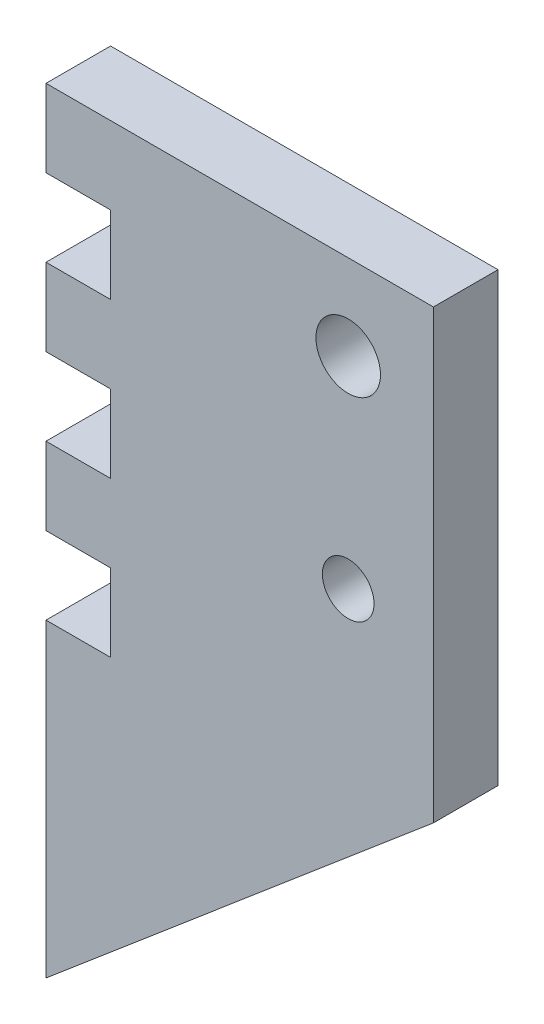
SolidWorks part; units mm, degrees
ref_plane "Front Plane" through (0, 0, 0) normal (0, 0, 1) x (1, 0, 0)
ref_plane "Top Plane" through (0, 0, 0) normal (0, 1, 0) x (1, 0, 0)
ref_plane "Right Plane" through (0, 0, 0) normal (1, 0, 0) x (0, 0, -1)
sketch "Sketch1" plane through (0, 0, 0) normal (0, 0, 1) x (1, 0, 0)
  line L0 (0, 0) -> (-38.1, 0)
  line L1 (0, 0) -> (0, -43.942)
  line L2 (-38.1, 0) -> (-38.1, -7.62)
  line L3 (-38.1, -7.62) -> (-31.75, -7.62)
  line L4 (-31.75, -7.62) -> (-31.75, -15.24)
  line L5 (-31.75, -15.24) -> (-38.1, -15.24)
  line L6 (-38.1, -45.72) -> (-38.1, -76.2)
  line L7 (-38.1, -15.24) -> (-38.1, -22.86)
  line L8 (-38.1, -22.86) -> (-31.75, -22.86)
  line L9 (-31.75, -22.86) -> (-31.75, -30.48)
  line L10 (-31.75, -30.48) -> (-38.1, -30.48)
  line L11 (-38.1, -30.48) -> (-38.1, -38.1)
  line L12 (-38.1, -38.1) -> (-31.75, -38.1)
  line L13 (-31.75, -38.1) -> (-31.75, -45.72)
  line L14 (-31.75, -45.72) -> (-38.1, -45.72)
  line L15 (-38.1, -76.2) -> (0, -43.942)
  circle A0 centre (-8.382, -8.382) radius 3.175
  circle A1 centre (-8.382, -28.194) radius 2.54
  point P23 (0, 0)
  point P24 (0, 0)
  dimension "D9" = 6.35
  dimension "D10" = 5.08
  dimension "D1" = 38.1
  dimension "D2" = 43.942
  dimension "D3" = 7.62
  dimension "D4" = 7.62
  dimension "D5" = 6.35
  dimension "D6" = 6.35
  dimension "D8" = 76.2
  dimension "D11" = 19.812
  dimension "D12" = 8.382
  dimension "D13" = 8.382
  dimension "D14" = 8.382
  dimension "D7" = 3
extrude "Boss-Extrude1" add sketch "Sketch1" along normal blind 6.35 contours L6 L15 L1 L0 L2 L3 L4 L5 L7 L8 L9 L10 L11 L12 L13 L14 A1 A0 region at (-20.0788, -31.4046, 0)
